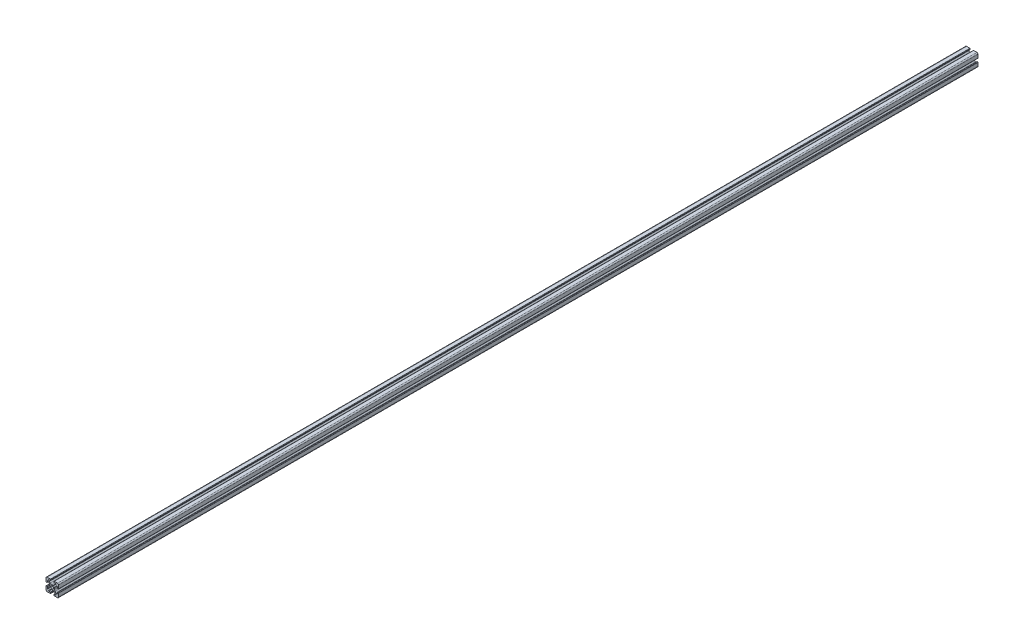
SolidWorks part; units mm, degrees
ref_plane "Front Plane" through (0, 0, 0) normal (0, 0, 1) x (1, 0, 0)
ref_plane "Top Plane" through (0, 0, 0) normal (0, 1, 0) x (1, 0, 0)
ref_plane "Right Plane" through (0, 0, 0) normal (1, 0, 0) x (0, 0, -1)
sketch "Sketch2" plane through (0, 0, 0) normal (0, 0, 1) x (1, 0, 0)
  line L0 (0, 10) -> (0, -10) construction
  line L1 (-10, 0) -> (10, 0) construction
  line L2 (2.5, -10) -> (10, -10)
  line L3 (10, -10) -> (10, -2.5)
  line L4 (2.5, -10) -> (2.5, -7.9246)
  line L5 (2.5, -7.9246) -> (6.4571, -7.9246)
  line L6 (6.4571, -7.9246) -> (2.1325, -3.6)
  line L7 (0, 0) -> (10, -10) construction
  line L8 (10, -2.5) -> (7.9246, -2.5)
  line L9 (7.9246, -2.5) -> (7.9246, -6.4571)
  line L10 (7.9246, -6.4571) -> (3.6, -2.1325)
  line L11 (5.7623, -4.2948) -> (4.2948, -5.7623) construction
  circle A0 centre (0, 0) radius 2.15
  arc A1 (5.25, -7.9246) -> (5.6036, -7.0711) centre (5.25, -7.4246) ccw construction
  point P8 (0, -3.6)
  point P16 (5.0286, -5.0286)
  dimension "Center Hole Diameter" = 4.3
  dimension "D3" = 0.5
  dimension "Rail Height" = 20
  dimension "Rail Width" = 20
  dimension "T-Slot Width" = 5
  dimension "Slot Depth" = 6.4
  dimension "Slot Inner Width" = 11.5
sketch "Sketch3" plane through (0, 0, 0) normal (1, 0, 0) x (0, 0, -1)
  line L0 (-730.72, -10) -> (730.72, -10) construction
  line L1 (-705.32, 0) -> (705.32, 0) construction
  line L2 (0, 10) -> (0, -10) construction
  line L3 (0, 10) -> (0, -10) construction
  point P6 (-705.32, 0)
  point P8 (705.32, 0)
  dimension "Length" = 1461.44
  dimension "D1" = 25.4
sketch "Sketch4" plane through (0, 0, 0) normal (0, 0, 1) x (1, 0, 0)
  line L0 (3, -10) -> (8.25, -10)
  line L1 (2.5, -10) -> (10, -10) construction
  line L2 (2.5, -10) -> (2.5, -7.9246) construction
  line L3 (2.5, -7.9246) -> (6.4571, -7.9246) construction
  line L4 (2.5, -8.4246) -> (2.5, -9.5)
  line L5 (3, -7.9246) -> (5.25, -7.9246)
  line L6 (0, -3.6) -> (0.8898, -3.6)
  line L7 (6.4571, -7.9246) -> (2.1325, -3.6) construction
  line L8 (3.0112, -4.4787) -> (5.6036, -7.0711)
  line L9 (10, -10) -> (10, -2.5) construction
  line L10 (7.9246, -6.4571) -> (3.6, -2.1325) construction
  line L11 (7.9246, -2.5) -> (7.9246, -6.4571) construction
  line L12 (7.9246, -5.25) -> (7.9246, -3)
  line L13 (10, -2.5) -> (7.9246, -2.5) construction
  line L14 (8.4246, -2.5) -> (9.5, -2.5)
  line L15 (10, -3) -> (10, -8.25)
  line L16 (7.0711, -5.6036) -> (4.4787, -3.0112)
  line L17 (3.6, 0) -> (3.6, -0.8898)
  line L18 (-10, 0) -> (10, 0) construction
  line L19 (0, -3.6) -> (0, -2.15)
  line L20 (0, 10) -> (0, -10) construction
  line L21 (3.6, 0) -> (2.15, 0)
  arc A0 (2.5, -9.5) -> (3, -10) centre (3, -9.5) ccw
  arc A1 (5.25, -7.9246) -> (5.6036, -7.0711) centre (5.25, -7.4246) ccw construction
  arc A2 (2.5, -8.4246) -> (3, -7.9246) centre (3, -8.4246) cw
  arc A3 (5.25, -7.9246) -> (5.6036, -7.0711) centre (5.25, -7.4246) ccw
  arc A4 (0.8898, -3.6) -> (3.0112, -4.4787) centre (0.8898, -6.6) cw
  arc A5 (8.25, -10) -> (10, -8.25) centre (8.25, -8.25) ccw
  arc A6 (7.0711, -5.6036) -> (7.9246, -5.25) centre (7.4246, -5.25) ccw
  arc A7 (7.9246, -3) -> (8.4246, -2.5) centre (8.4246, -3) cw
  arc A8 (9.5, -2.5) -> (10, -3) centre (9.5, -3) cw
  arc A9 (4.4787, -3.0112) -> (3.6, -0.8898) centre (6.6, -0.8898) cw
  circle A10 centre (0, 0) radius 2.15 construction
  arc A11 (0, -2.15) -> (2.15, 0) centre (0, 0) ccw
  dimension "D1" = 1.75
  dimension "D2" = 3
extrude "Boss-Extrude1" add sketch "Sketch4" along normal mid plane 1461.44
mirror "Mirror1" about plane through (0, 0, 0) normal (1, 0, 0) of bodies 134
mirror "Mirror2" about plane through (0, 0, 0) normal (0, 1, 0) of bodies 135
equation "\"D3@Sketch2\"=\"T-Slot Width@Sketch2\"*0.1"
equation "\"D1@Sketch4\"=\"D3@Sketch2\"*3.5"
equation "\"D2@Sketch4\"=\"D3@Sketch2\"*6"
equation "\"D1@Boss-Extrude1\"=\"Length@Sketch3\""
